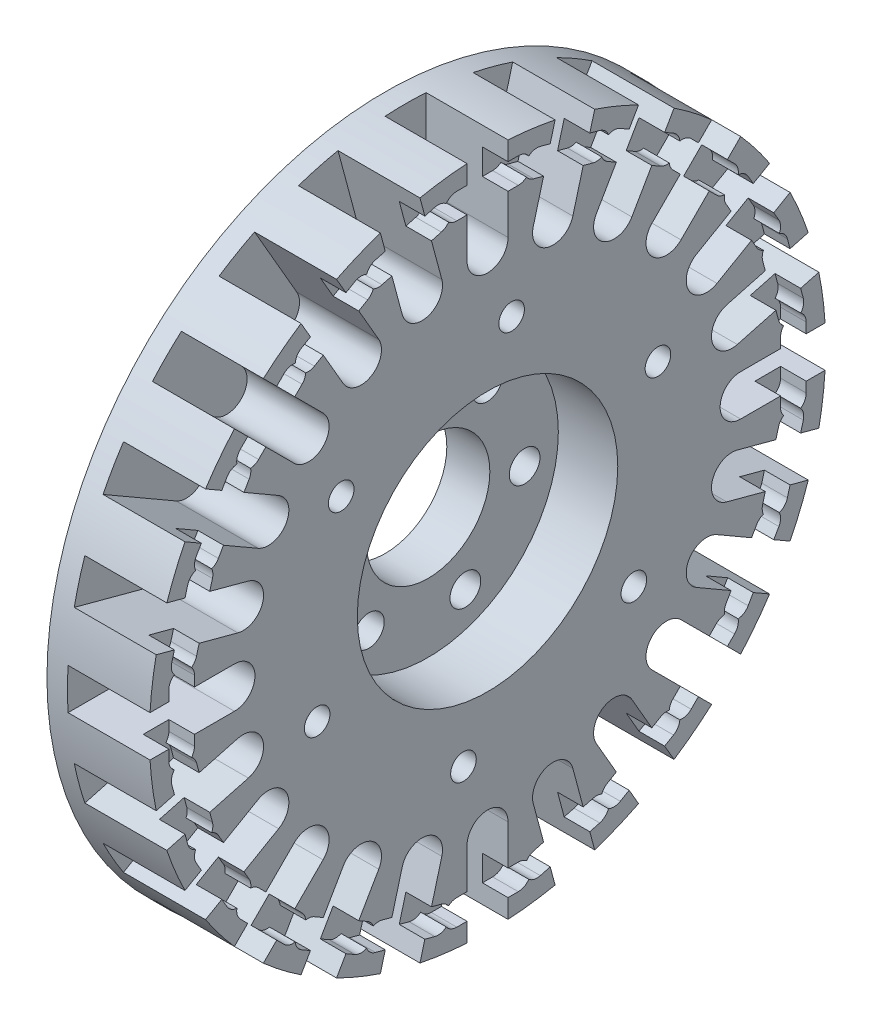
SolidWorks part; units mm, degrees
material "1060 Alloy"
ref_plane "Front Plane" through (0, 0, 0) normal (0, 0, 1) x (1, 0, 0)
ref_plane "Top Plane" through (0, 0, 0) normal (0, 1, 0) x (1, 0, 0)
ref_plane "Right Plane" through (0, 0, 0) normal (1, 0, 0) x (0, 0, -1)
sketch "Sketch1" plane through (0, 0, 0) normal (1, 0, 0) x (0, 0, -1)
  circle A0 centre (0, 0) radius 33
  circle A1 centre (0, 0) radius 6.025
  dimension "D1" = 66
  dimension "D2" = 12.05
extrude "Boss-Extrude1" add sketch "Sketch1" along normal blind 10
sketch "Sketch2" plane through (10, 0, 0) normal (1, 0, 0) x (0, 0, -1)
  line L0 (-2, 33) -> (2, 33)
  line L1 (2, 33) -> (2, 24.7)
  line L2 (-2, 24.7) -> (-2, 33)
  arc A0 (2, 24.7) -> (-2, 24.7) centre (0, 24.7) cw
  circle A1 centre (0, 0) radius 33 construction
  dimension "D1" = 4
  dimension "D2" = 8.3
extrude "Cut-Extrude1" cut sketch "Sketch2" against normal blind 8
sketch "Sketch3" plane through (10, 0, 0) normal (1, 0, 0) x (0, 0, -1)
  line L0 (-3, 29.85) -> (3, 29.85) construction
  line L1 (-3, 31.1) -> (3, 31.1)
  line L2 (-3, 28.6) -> (3, 28.6)
  arc A0 (-3, 31.1) -> (-3, 28.6) centre (-3, 29.85) ccw
  arc A1 (3, 28.6) -> (3, 31.1) centre (3, 29.85) ccw
  arc A2 (-2, 24.7) -> (2, 24.7) centre (0, 24.7) ccw construction
  point P2 (0, 29.85)
  dimension "D1" = 1.25
  dimension "D2" = 5.15
  dimension "D3" = 6
extrude "Cut-Extrude2" cut sketch "Sketch3" against normal blind 2.5
pattern_circular "CirPattern1" count 24 over 360 about axis through (10, 0, 0) along (1, 0, 0) of "Cut-Extrude1", "Cut-Extrude2"
hole_wizard "Tap Drill for M3x0.5 Tap1" positions "Sketch6" profile "Sketch5" hole size "M3x0.5" standard "ANSI Metric" end condition up to next
sketch "Sketch6" plane through (10, 0, 0) normal (1, 0, 0) x (0, 0, -1)
  line L0 (2.3495, 17.846) -> (0, 0) construction
  line L1 (0, 0) -> (6.025, 0) construction
  circle A2 centre (0, 0) radius 6.025 construction
  point P0 (2.3495, 17.846)
  dimension "D1" = 82.5
  dimension "D2" = 18
sketch "Sketch5" plane through (10, 17.846, -2.3495) normal (0, 1, 0) x (0, 0, -1)
  line L0 (0, 0) -> (0, 10.001)
  line L1 (0, 10.001) -> (1.25, 10.001)
  line L2 (1.25, 10.001) -> (1.25, 0)
  line L5 (1.25, 0) -> (0, 0)
  line L11 (0, -6.35) -> (0, 107.95) construction
  dimension "Thru Hole Dia." = 2.5
  dimension "Thru Hole Depth" = 10.001
pattern_circular "CirPattern2" count 6 over 360 about axis through (10, 0, 0) along (1, 0, 0) of "Tap Drill for M3x0.5 Tap1"
sketch "Sketch7" plane through (10, 0, 0) normal (-1, 0, 0) x (0, 0, 1)
  circle A0 centre (0, 0) radius 12.71
  dimension "D1" = 25.42
extrude "Cut-Extrude3" cut sketch "Sketch7" along normal offset from surface (5.8 mm away) 4.2 up to face at (0, 6.8883, -17.8798)
sketch "Sketch11" plane through (10, 0, 0) normal (1, 0, 0) x (0, 0, -1)
  line L0 (0, 0) -> (-10.5081, 0) construction
  line L1 (-3.6355, 8.7769) -> (0, 0) construction
  circle A0 centre (-3.6355, 8.7769) radius 1.5
  dimension "D1" = 3
  dimension "D2" = 9.5
  dimension "D3" = 67.5
extrude "Cut-Extrude4" cut sketch "Sketch11" against normal up to next
chamfer "Chamfer1" distance 1.5 angle 45 1 edges at (0, 8.7769, 2.1355)
pattern_circular "CirPattern3" count 6 over 360 about axis through (0, 0, 0) along (1, 0, 0) of "Cut-Extrude4", "Chamfer1"
